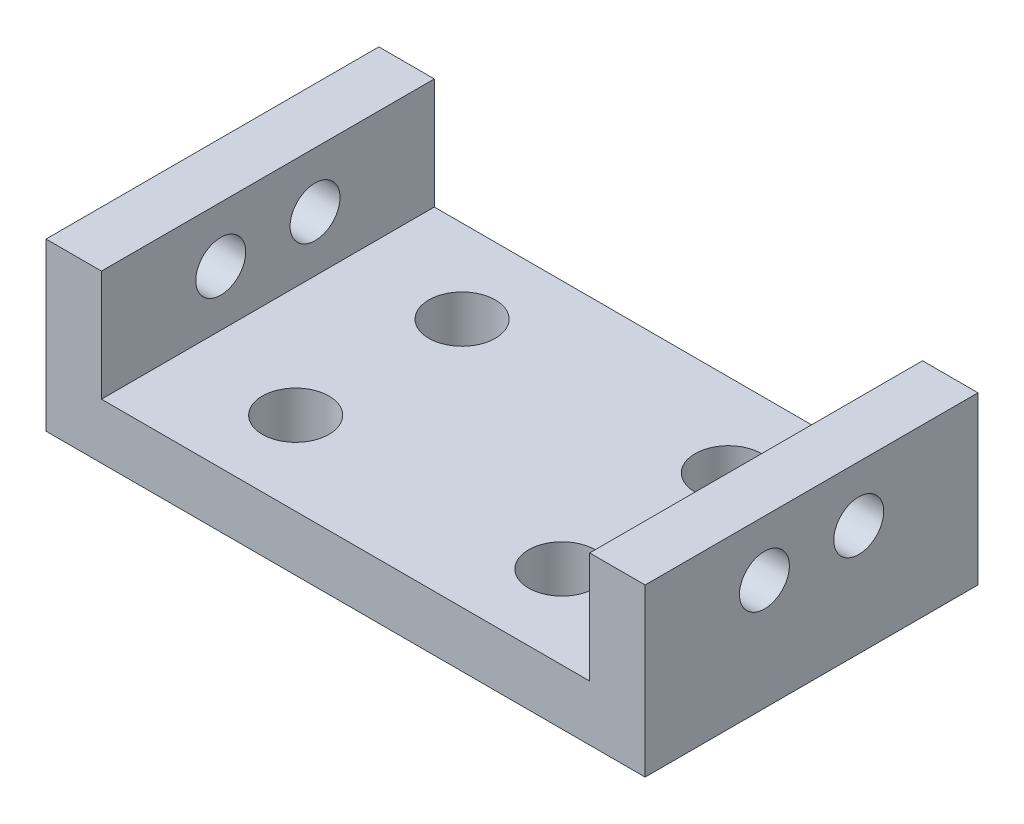
SolidWorks part; units mm, degrees
ref_plane "Front Plane" through (0, 0, 0) normal (0, 0, 1) x (1, 0, 0)
ref_plane "Top Plane" through (0, 0, 0) normal (0, 1, 0) x (1, 0, 0)
ref_plane "Right Plane" through (0, 0, 0) normal (1, 0, 0) x (0, 0, -1)
sketch "Sketch1" plane through (0, 0, 0) normal (0, 1, 0) x (1, 0, 0)
  line L1 (27, -15) -> (-27, -15)
  line L2 (27, -15) -> (27, 15)
  line L3 (27, 15) -> (-27, 15)
  line L4 (-27, -15) -> (-27, 15)
  line L5 (27, -15) -> (-27, 15) construction
  line L6 (27, 15) -> (-27, -15) construction
  point P0 (0, 0)
  dimension "D1" = 54
  dimension "D2" = 30
extrude "Boss-Extrude1" add sketch "Sketch1" along normal blind 15
sketch "Sketch2" plane through (0, 0, -15) normal (0, 0, -1) x (-1, 0, 0)
  line L0 (-27, 15) -> (27, 15) construction
  line L1 (-22, 15) -> (22, 15)
  line L2 (-22, 15) -> (-22, 5)
  line L3 (-22, 5) -> (22, 5)
  line L4 (22, 15) -> (22, 5)
  line L5 (-27, 15) -> (-27, 0) construction
  line L6 (27, 15) -> (27, 0) construction
  line L7 (-27, 0) -> (27, 0) construction
  dimension "D1" = 5
  dimension "D2" = 5
  dimension "D3" = 5
extrude "Cut-Extrude1" cut sketch "Sketch2" against normal through all
sketch "Sketch3" plane through (-27, 0, 0) normal (-1, 0, 0) x (0, 0, 1)
  line L0 (-15, 15) -> (15, 15) construction
  line L1 (-15, 15) -> (-15, 0) construction
  circle A0 centre (-4.25, 10) radius 2.25
  circle A1 centre (4.25, 10) radius 2.25
  dimension "D1" = 4.5
  dimension "D2" = 4.5
  dimension "D3" = 5
  dimension "D4" = 5
  dimension "D5" = 8.5
  dimension "D6" = 10.75
ref_plane "Plane1" through (0, 0, 0) normal (1, 0, 0) x (0, 0, -1)
extrude "Cut-Extrude2" cut sketch "Sketch3" against normal through all
hole_wizard "Ø6.0mm Dowel Hole2" positions "3DSketch2" profile "Sketch7" hole size "Ø6.0" standard "ANSI Metric" end condition through all
sketch3d "3DSketch2"
  line L0 (-27, 0, -15) -> (-27, 0, 15) construction
  line L1 (27, 0, 15) -> (27, 0, -15) construction
  line L2 (-27, 0, 15) -> (27, 0, 15) construction
  point P0 (-12, 0, 7.5)
  point P2 (12, 0, 7.5)
  point P4 (12, 0, -7.5)
  point P6 (-12, 0, -7.5)
  point P18 (0, 0, 0)
  dimension "D1" = 15
  dimension "D2" = 15
  dimension "D3" = 15
  dimension "D4" = 15
  dimension "D5" = 15
  dimension "D6" = 15
  dimension "D7" = 7.5
  dimension "D8" = 7.5
sketch "Sketch7" plane through (-12, 0, 7.5) normal (1, 0, 0) x (0, 0, -1)
  line L0 (0, 0) -> (0, 15)
  line L1 (0, 15) -> (3, 15)
  line L2 (3, 15) -> (3, 0)
  line L5 (3, 0) -> (0, 0)
  line L11 (0, -6.35) -> (0, 107.95) construction
  dimension "Thru Hole Dia." = 6
  dimension "Thru Hole Depth" = 15
